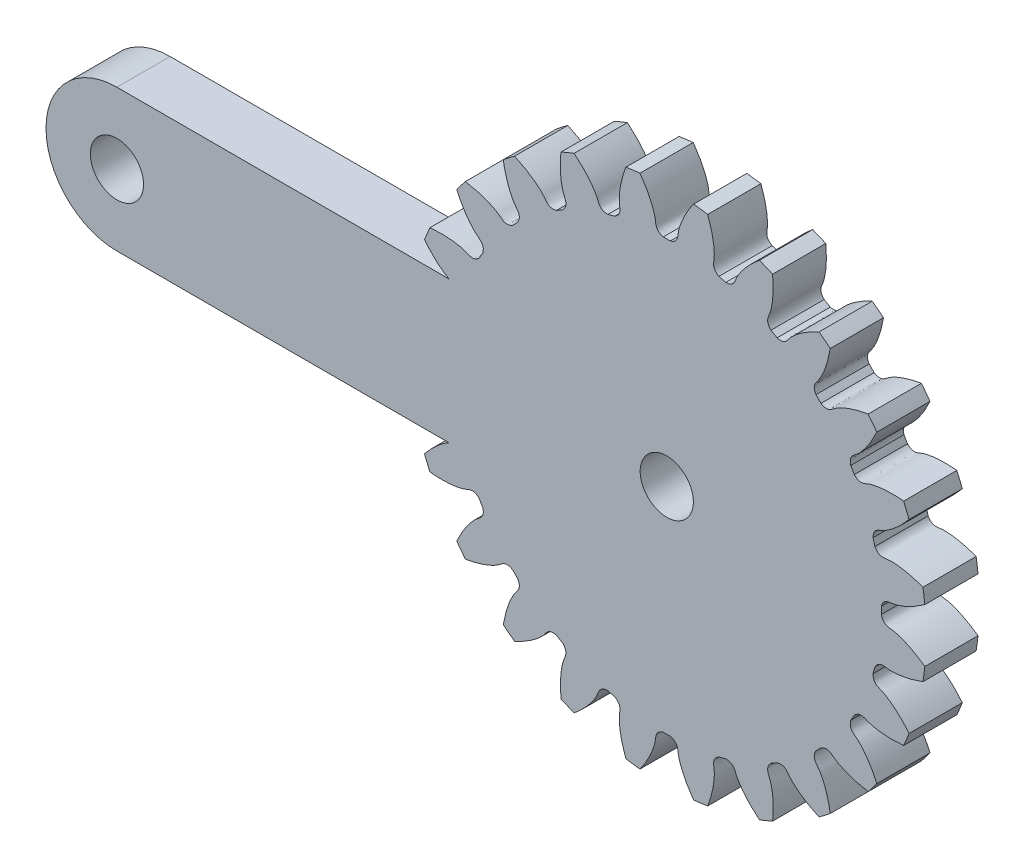
SolidWorks part; units mm, degrees
ref_plane "前视基准面" through (0, 0, 0) normal (0, 0, 1) x (1, 0, 0)
ref_plane "上视基准面" through (0, 0, 0) normal (0, 1, 0) x (1, 0, 0)
ref_plane "右视基准面" through (0, 0, 0) normal (1, 0, 0) x (0, 0, -1)
other "Configuration Table"
sketch "草图1" plane through (0, 0, 0) normal (0, 0, 1) x (1, 0, 0)
  circle A0 centre (0, 0) radius 14.625
extrude "凸台-拉伸1" add sketch "草图1" along normal blind 3
ref_axis "基准轴1" through (0, 0, -1.5) along (0, 0, 1)
sketch "草图2" plane through (0, 0, 0) normal (0, 0, 1) x (1, 0, 0)
  line L0 (0, 0) -> (0, 14.625) construction
  circle A0 centre (0, 0) radius 14.625 construction
  arc A1 (0.1989, 12.0921) -> (-0.1989, 12.0921) centre (0, 0) ccw
  arc A2 (3.5051, 16.5309) -> (-3.5051, 16.5309) centre (0, 0) ccw
  spline S0 degree 3 poles (0.1989, 12.0921) (0.6389, 12.214) (0.6064, 12.5052) (0.6596, 12.7943) (0.6672, 12.8316) (0.6766, 12.8736) (0.6881, 12.9205) (0.7019, 12.9719) (0.7181, 13.028) (0.7369, 13.0886) (0.7585, 13.1536) (0.7831, 13.2229) (0.8109, 13.2965) (0.842, 13.3743) (0.8767, 13.456) (0.915, 13.5417) (0.9572, 13.6312) (1.0035, 13.7244) (1.054, 13.8211) (1.1088, 13.9213) (1.1681, 14.0247) (1.2321, 14.1313) (1.3009, 14.2409) (1.3747, 14.3533) (1.4536, 14.4684) (1.5377, 14.5861) (1.6272, 14.7061) (1.7222, 14.8283) (1.8228, 14.9525) (1.9292, 15.0786) (2.0414, 15.2063) (2.1595, 15.3355) (2.2837, 15.466) (2.4141, 15.5975) (2.5507, 15.73) (2.6936, 15.8632) (2.843, 15.9969) (2.9988, 16.1309) (3.218, 16.3118) (3.3884, 16.444) (3.5051, 16.5309) knots 0 0 0 0 0.143961 0.149818 0.156577 0.164236 0.172796 0.182258 0.19262 0.203884 0.216049 0.229115 0.243082 0.25795 0.273719 0.290389 0.30796 0.326433 0.345806 0.366081 0.387257 0.409333 0.432311 0.45619 0.48097 0.506651 0.533234 0.560717 0.589101 0.618387 0.648574 0.679661 0.71165 0.74454 0.778331 0.813023 0.848616 0.885111 0.922506 1 1 1 1
  spline S1 degree 3 poles (-0.1989, 12.0921) (-0.6389, 12.214) (-0.6064, 12.5052) (-0.6596, 12.7943) (-0.6672, 12.8316) (-0.6766, 12.8736) (-0.6881, 12.9205) (-0.7019, 12.9719) (-0.7181, 13.028) (-0.7369, 13.0886) (-0.7585, 13.1536) (-0.7831, 13.2229) (-0.8109, 13.2965) (-0.842, 13.3743) (-0.8767, 13.456) (-0.915, 13.5417) (-0.9572, 13.6312) (-1.0035, 13.7244) (-1.054, 13.8211) (-1.1088, 13.9213) (-1.1681, 14.0247) (-1.2321, 14.1313) (-1.3009, 14.2409) (-1.3747, 14.3533) (-1.4536, 14.4684) (-1.5377, 14.5861) (-1.6272, 14.7061) (-1.7222, 14.8283) (-1.8228, 14.9525) (-1.9292, 15.0786) (-2.0414, 15.2063) (-2.1595, 15.3355) (-2.2837, 15.466) (-2.4141, 15.5975) (-2.5507, 15.73) (-2.6936, 15.8632) (-2.843, 15.9969) (-2.9988, 16.1309) (-3.218, 16.3118) (-3.3884, 16.444) (-3.5051, 16.5309) knots 0 0 0 0 0.143961 0.149818 0.156577 0.164236 0.172796 0.182258 0.19262 0.203884 0.216049 0.229115 0.243082 0.25795 0.273719 0.290389 0.30796 0.326433 0.345806 0.366081 0.387257 0.409333 0.432311 0.45619 0.48097 0.506651 0.533234 0.560717 0.589101 0.618387 0.648574 0.679661 0.71165 0.74454 0.778331 0.813023 0.848616 0.885111 0.922506 1 1 1 1
extrude "切除-拉伸1" cut sketch "草图2" along normal through all
pattern_circular "阵列(圆周)1" count 24 every 15 about axis through (0, 0, -1.5) along (0, 0, 1) of "切除-拉伸1"
sketch "草图3" plane through (0, 0, 0) normal (0, 0, 1) x (1, 0, 0)
  circle A0 centre (0, 0) radius 13.5 construction
  dimension "Dn" = 27
sketch "草图4" plane through (0, 0, 3) normal (0, 0, 1) x (1, 0, 0)
  line L0 (0, 0) -> (-31, 0) construction
  line L1 (0, -4) -> (-31, -4)
  line L2 (0, 4) -> (-31, 4)
  arc A1 (0, -4) -> (0, 4) centre (0, 0) ccw
  arc A2 (-31, 4) -> (-31, -4) centre (-31, 0) ccw
  circle A3 centre (-31, 0) radius 1.5
  point P4 (-15.5, 0)
  dimension "D1" = 31
  dimension "D3" = 3
  dimension "D2" = 8
extrude "凸台-拉伸2" add sketch "草图4" against normal blind 3
sketch "草图6" plane through (0, 0, 3) normal (0, 0, 1) x (1, 0, 0)
  circle A0 centre (0, 0) radius 1.5
  dimension "D1" = 3
extrude "切除-拉伸3" cut sketch "草图6" against normal blind 3
